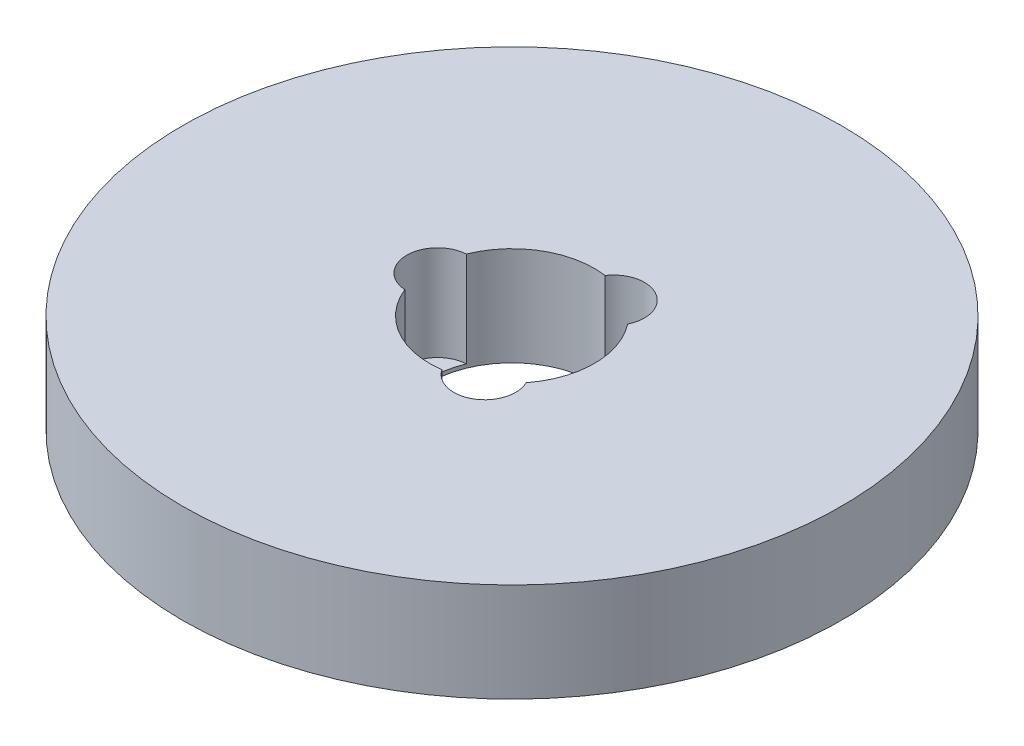
SolidWorks part; units mm, degrees
ref_plane "Front Plane" through (0, 0, 0) normal (0, 0, 1) x (1, 0, 0)
ref_plane "Top Plane" through (0, 0, 0) normal (0, 1, 0) x (1, 0, 0)
ref_plane "Right Plane" through (0, 0, 0) normal (1, 0, 0) x (0, 0, -1)
sketch "Sketch1" plane through (0, 0, 0) normal (0, 1, 0) x (1, 0, 0)
  circle A0 centre (0, 0) radius 30
  dimension "FLANGE_OD" = 60
extrude "Boss-Extrude1" add sketch "Sketch1" along normal blind 9
sketch "Sketch2" plane through (0, 0, 0) normal (0, 1, 0) x (1, 0, 0)
  circle A0 centre (0, 0) radius 7.5
  dimension "BORE_D" = 15
extrude "Cut-Extrude1" cut sketch "Sketch2" along normal through all
sketch "Sketch3" plane through (0, 9, 0) normal (0, 1, 0) x (1, 0, 0)
  circle A0 centre (0, 0) radius 6.7687 construction
  circle A1 centre (-6.7687, 0) radius 2.8133
  dimension "BOLT_D" = 5.6266
  dimension "BOLT_PCD" = 13.5374
extrude "Cut-Extrude2" cut sketch "Sketch3" against normal blind 8.6566
pattern_circular "CirPattern1" count 3 over 360 about axis through (0, 0, 0) along (0, 1, 0) of "Cut-Extrude2"
